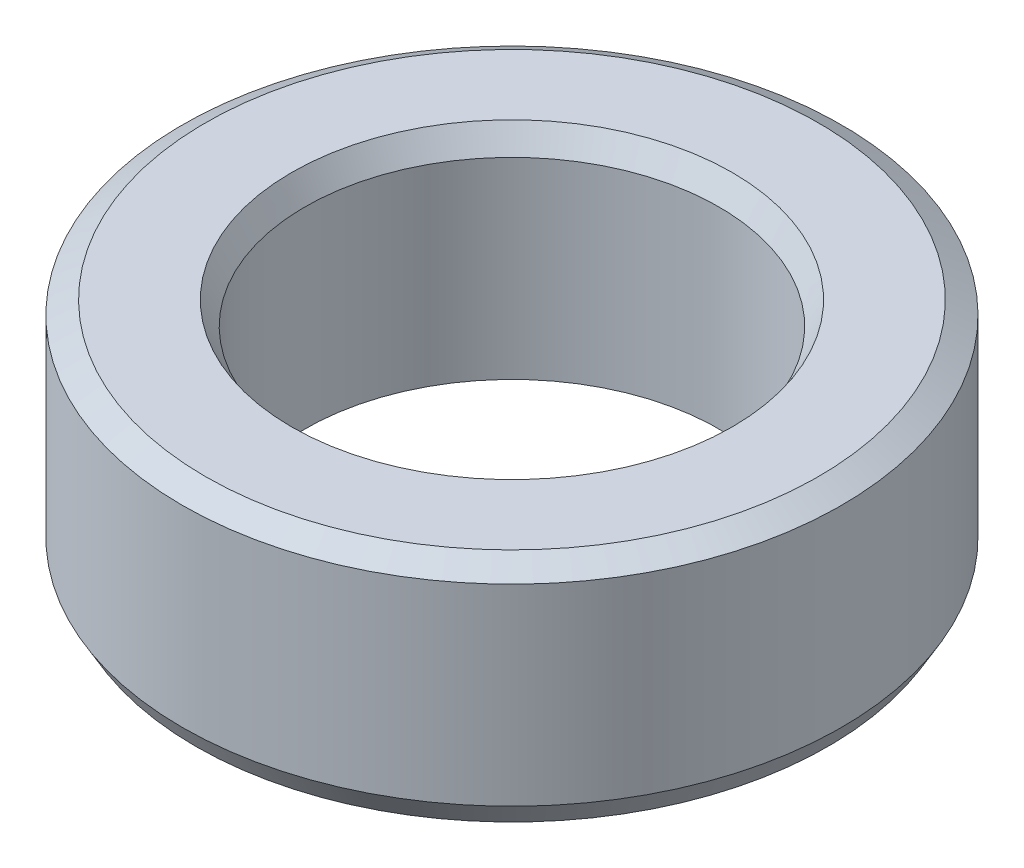
SolidWorks part; units mm, degrees
ref_plane "Front Plane" through (0, 0, 0) normal (0, 0, 1) x (1, 0, 0)
ref_plane "Top Plane" through (0, 0, 0) normal (0, 1, 0) x (1, 0, 0)
ref_plane "Right Plane" through (0, 0, 0) normal (1, 0, 0) x (0, 0, -1)
sketch "Sketch1" plane through (0, 0, 0) normal (0, 1, 0) x (1, 0, 0)
  circle A0 centre (0, 0) radius 20
  dimension "SLEEVE_OD" = 40
extrude "Boss-Extrude1" add sketch "Sketch1" along normal blind 13.8836
sketch "Sketch2" plane through (0, 0, 0) normal (0, 1, 0) x (1, 0, 0)
  circle A0 centre (0, 0) radius 12.5629
  dimension "BORE_D" = 25.1259
extrude "Cut-Extrude1" cut sketch "Sketch2" along normal through all
chamfer "Chamfer1" distance 0.8095 angle 60 4 edges at (0, 13.8836, 12.5629) (0, 0, 12.5629) (0, 0, 20) (0, 13.8836, 20) first distance on face at (0, 13.8836, 12.5629) first distance on face at (0, 0, 12.5629) first distance on face at (0, 13.8836, 20)
